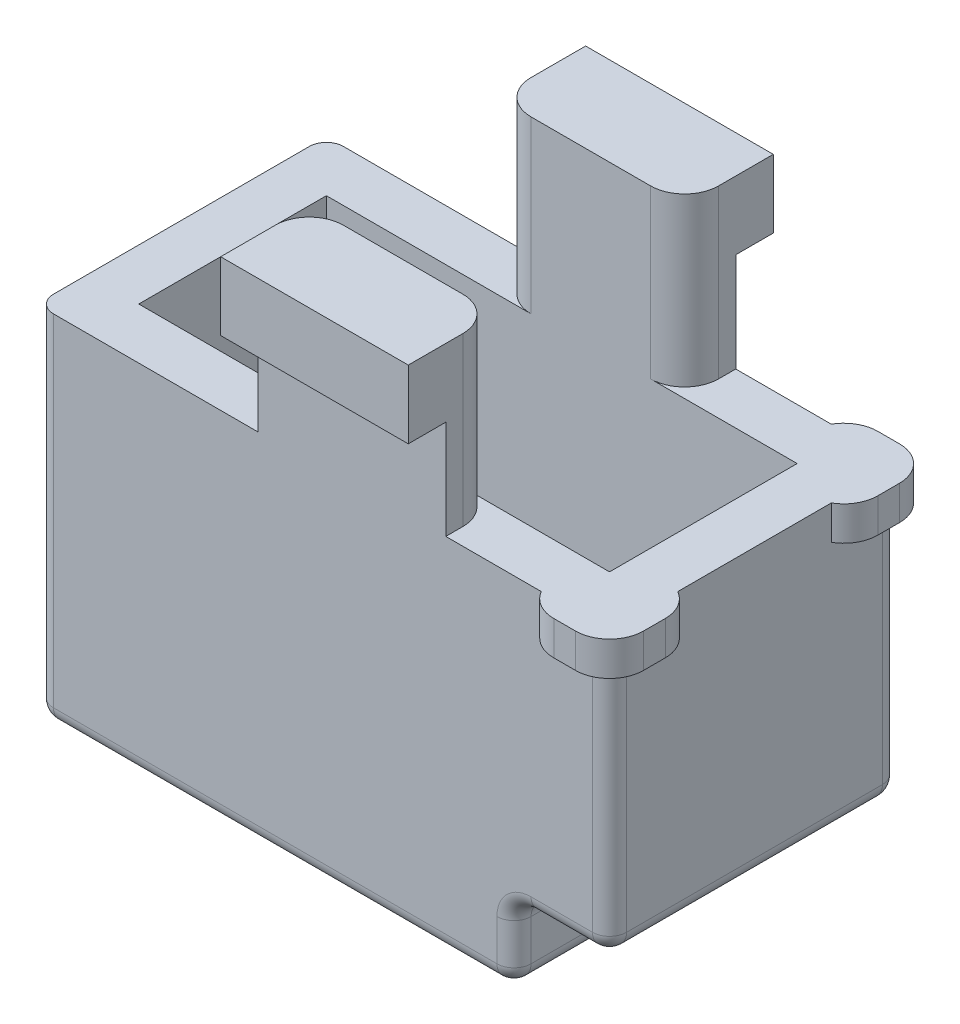
SolidWorks part; units mm, degrees
ref_plane "Front Plane" through (0, 0, 0) normal (0, 0, 1) x (1, 0, 0)
ref_plane "Top Plane" through (0, 0, 0) normal (0, 1, 0) x (1, 0, 0)
ref_plane "Right Plane" through (0, 0, 0) normal (1, 0, 0) x (0, 0, -1)
sketch "Sketch1" plane through (0, 0, 0) normal (0, 0, 1) x (1, 0, 0)
  line L0 (0, 0) -> (-6.5, 0)
  line L1 (-6.5, 0) -> (-6.5, -10.5)
  line L2 (-6.5, -10.5) -> (7.5, -10.5)
  line L3 (7.5, -10.5) -> (7.5, -8.3)
  line L4 (7.5, -8.3) -> (10.3, -8.3)
  line L5 (10.3, -8.3) -> (10.3, 0.1)
  line L6 (10.3, 0.1) -> (5.5, 0.1)
  line L7 (5.5, 0.1) -> (5.5, 5)
  line L8 (5.5, 5) -> (0, 5)
  line L9 (0, 5) -> (0, 0)
  dimension "D1" = 6.5
  dimension "D2" = 10.5
  dimension "D3" = 2.2
  dimension "D4" = 14
  dimension "D5" = 2.8
  dimension "D6" = 8.4
  dimension "D7" = 5.5
  dimension "D8" = 5
  dimension "D9" = 4.8
extrude "Boss-Extrude1" add sketch "Sketch1" along normal blind 8.5
shell "Shell1" thickness 1.5 removed face at (0.5, -10.5, 4.25) removed face at (-3.25, 0, 4.25) removed face at (0, 2.5, 4.25) removed face at (5.5, 2.55, 4.25) removed face at (7.9, 0.1, 4.25) removed face at (2.75, 5, 4.25)
sketch "Sketch3" plane through (0, -10.5, 0) normal (0, -1, 0) x (1, 0, 0)
  line L0 (7.5, 8.5) -> (7.5, 0) construction
  line L1 (-6.5, 0) -> (7.5, 0) construction
  line L2 (-6.5, 8.5) -> (-6.5, 0) construction
  line L3 (-6.5, 8.5) -> (7.5, 8.5) construction
  line L4 (7.5, 8.5) -> (7.5, 0)
  line L5 (-6.5, 0) -> (7.5, 0)
  line L6 (-6.5, 8.5) -> (-6.5, 0)
  line L7 (-6.5, 8.5) -> (7.5, 8.5)
extrude "Boss-Extrude2" add sketch "Sketch3" against normal blind 1.5
sketch "Sketch4" plane through (0, -10.5, 0) normal (0, -1, 0) x (1, 0, 0)
  line L0 (-2.7122, 4.2485) -> (5.9728, 4.2485) construction
  line L1 (-6.5, 8.5) -> (-6.5, 0) construction
  line L5 (-3, 3.75) -> (-4.0583, 1.9169)
  line L6 (-1.8453, 3.75) -> (-0.4641, 3.75)
  line L7 (-3.1923, 1.4169) -> (-1.8453, 3.75)
  line L8 (-0.4641, 3.75) -> (-1.5224, 1.9169)
  line L9 (-0.6564, 1.4169) -> (0.6906, 3.75)
  line L10 (2.0718, 3.75) -> (1.0135, 1.9169)
  line L11 (1.8795, 1.4169) -> (3.2265, 3.75)
  line L12 (4.6077, 3.75) -> (3.5494, 1.9169)
  line L13 (4.4154, 1.4169) -> (5.7624, 3.75)
  line L14 (0.6906, 3.75) -> (2.0718, 3.75)
  line L15 (3.2265, 3.75) -> (4.6077, 3.75)
  line L16 (-3, 4.7469) -> (-2.8565, 4.4985)
  line L17 (-3, 3.75) -> (-2.8565, 3.9985)
  line L18 (3.2265, 4.7469) -> (4.6077, 4.7469)
  line L19 (0.6906, 4.7469) -> (2.0718, 4.7469)
  line L20 (4.4154, 7.08) -> (5.7624, 4.7469)
  line L21 (4.6077, 4.7469) -> (3.5494, 6.58)
  line L22 (1.8795, 7.08) -> (3.2265, 4.7469)
  line L23 (2.0718, 4.7469) -> (1.0135, 6.58)
  line L24 (-0.6564, 7.08) -> (0.6906, 4.7469)
  line L25 (-0.4641, 4.7469) -> (-1.5224, 6.58)
  line L26 (-3.1923, 7.08) -> (-1.8453, 4.7469)
  line L27 (-1.8453, 4.7469) -> (-0.4641, 4.7469)
  line L28 (-3, 4.7469) -> (-4.0583, 6.58)
  line L30 (5.7624, 4.7469) -> (5.9059, 4.4985)
  line L31 (5.7624, 3.75) -> (5.9059, 3.9985)
  arc A0 (-4.0583, 1.9169) -> (-3.1923, 1.4169) centre (-3.6253, 1.6669) ccw
  arc A1 (-1.5224, 1.9169) -> (-0.6564, 1.4169) centre (-1.0894, 1.6669) ccw
  arc A2 (1.0135, 1.9169) -> (1.8795, 1.4169) centre (1.4465, 1.6669) ccw
  arc A3 (3.5494, 1.9169) -> (4.4154, 1.4169) centre (3.9824, 1.6669) ccw
  arc A4 (3.5494, 6.58) -> (4.4154, 7.08) centre (3.9824, 6.83) cw
  arc A5 (1.0135, 6.58) -> (1.8795, 7.08) centre (1.4465, 6.83) cw
  arc A6 (-1.5224, 6.58) -> (-0.6564, 7.08) centre (-1.0894, 6.83) cw
  arc A7 (-4.0583, 6.58) -> (-3.1923, 7.08) centre (-3.6253, 6.83) cw
  arc A8 (-2.8565, 3.9985) -> (-2.8565, 4.4985) centre (-3.2896, 4.2485) ccw
  arc A9 (5.9059, 3.9985) -> (5.9059, 4.4985) centre (5.4728, 4.2485) ccw
  dimension "D5" = 4
  dimension "D2" = 1
  dimension "D3" = 1
  dimension "D1" = 1
  dimension "D4" = 3.5
extrude "Cut-Extrude1" cut sketch "Sketch4" against normal blind 0.5
sketch "Sketch5" plane through (0, 0.1, 0) normal (0, 1, 0) x (1, 0, 0)
  line L1 (8.3, 0.5) -> (10.8, 0.5)
  line L2 (10.8, 0.5) -> (10.8, -2)
  line L3 (10.8, -2) -> (10.3, -2)
  line L4 (10.3, -0.75) -> (10.8, -0.75) construction
  line L5 (10.3, 0) -> (5.5, 0) construction
  line L6 (10.3, -8.5) -> (10.3, 0) construction
  line L7 (10.3, -8.5) -> (10.3, 0)
  line L8 (10.3, 0) -> (8.3, 0)
  line L9 (8.3, 0) -> (8.3, 0.5)
  line L11 (-6.5, -4.25) -> (10.3, -4.25)
  line L12 (-6.5, -8.5) -> (-6.5, 0) construction
  line L13 (8.3, -1.5) -> (8.3, -2)
  line L15 (10.8, 0.5) -> (10.3, 0.5)
  line L16 (8.3, -2) -> (10.8, -2)
  line L17 (10.3, -7.75) -> (10.8, -7.75) construction
  line L18 (10.3, -6.5) -> (10.8, -6.5)
  line L19 (10.8, -9) -> (10.3, -9)
  line L22 (8.3, -8.5) -> (8.3, -9)
  line L23 (10.3, -8.5) -> (8.3, -8.5)
  line L24 (10.8, -6.5) -> (10.3, -6.5)
  line L25 (10.8, -9) -> (10.8, -6.5)
  line L26 (8.3, -9) -> (10.8, -9)
  line M9 (5.5, -8.5) -> (10.3, -8.5)
  line M10 (10.3, -8.5) -> (10.3, 0)
  line M11 (10.3, 0) -> (5.5, 0)
  dimension "D1" = 2.5
  dimension "D2" = 2.5
  dimension "D3" = 0.5
  dimension "D4" = 0.5
extrude "Boss-Extrude4" add sketch "Sketch5" against normal blind 1 contours L9 L3 L2 L1 M11 M10 | L22 L26 L19 L25 L18 M10 M9 region at (10.55, 0.1, 6.5354) region at (9.3, 0.1, -0.4646)
fillet "Fillet2" radius 1 6 edges at (8.3, -0.4, -0.5) (10.8, -0.4, 2) (10.8, -0.4, -0.5) (8.3, -0.4, 9) (10.8, -0.4, 6.5) (10.8, -0.4, 9)
sketch "Sketch6" plane through (0, 5, 0) normal (0, 1, 0) x (1, 0, 0)
  line L0 (0, -7) -> (0, -9.6)
  line L1 (0, -9.6) -> (5.5, -9.6)
  line L2 (5.5, -7) -> (5.5, -9.6)
  line L3 (0, -7) -> (5.5, -7)
  line L4 (-5, -4.25) -> (8.8, -4.25) construction
  line L5 (-5, -7) -> (-5, -1.5) construction
  line L6 (8.8, -7) -> (8.8, -1.5) construction
  line L7 (0, -1.5) -> (5.5, -1.5)
  line L8 (5.5, -1.5) -> (5.5, 1.1)
  line L9 (0, 1.1) -> (5.5, 1.1)
  line L10 (0, -1.5) -> (0, 1.1)
  dimension "D1" = 2.6
extrude "Boss-Extrude5" add sketch "Sketch6" against normal blind 2
fillet "Fillet3" radius 0.5 14 edges at (8.9, -8.3, 8.5) (8.9, -8.3, 0) (-6.5, -5.25, 0) (-6.5, -5.25, 8.5) (-6.5, -10.5, 4.25) (10.3, -4.6, 8.5) (10.3, -4.6, 0) (10.3, -8.3, 4.25) (7.5, -8.3, 4.25) (7.5, -9.4, 0) (7.5, -9.4, 8.5) (0.5, -10.5, 8.5) (0.5, -10.5, 0) (7.5, -10.5, 4.25)
fillet "Fillet4" radius 1 4 edges at (0, 2.5, 1.5) (5.5, 2.55, 7) (0, 2.5, 7) (5.5, 2.55, 1.5)
